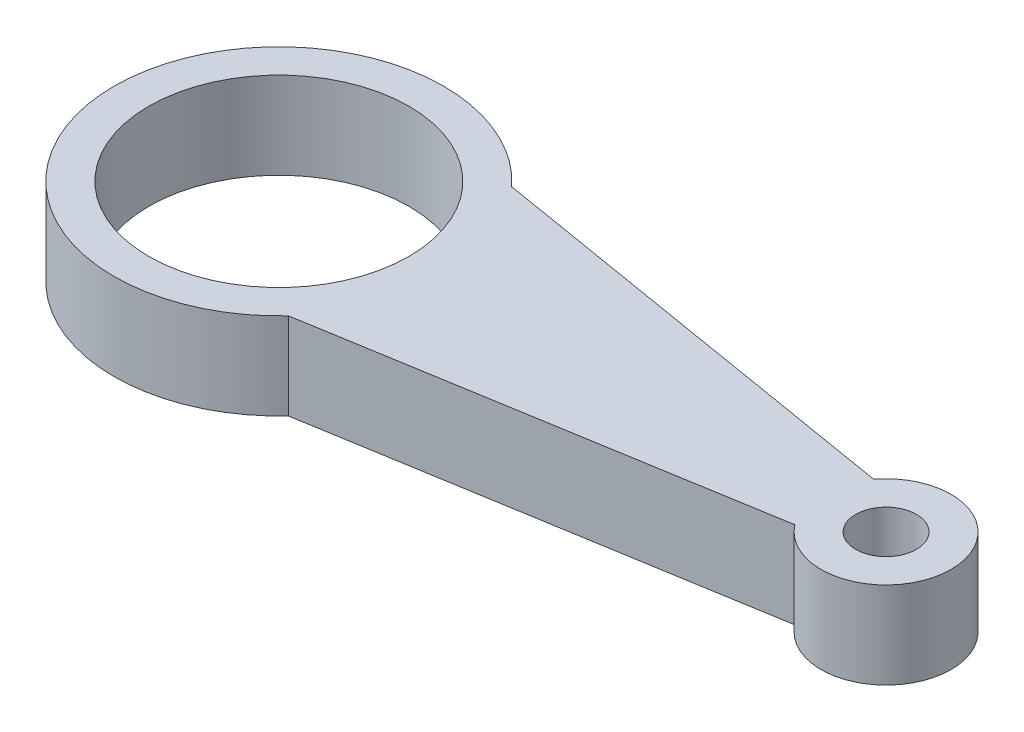
SolidWorks part; units mm, degrees
ref_plane "Front Plane" through (0, 0, 0) normal (0, 0, 1) x (1, 0, 0)
ref_plane "Top Plane" through (0, 0, 0) normal (0, 1, 0) x (1, 0, 0)
ref_plane "Right Plane" through (0, 0, 0) normal (1, 0, 0) x (0, 0, -1)
sketch "Sketch1" plane through (0, 0, 0) normal (0, 1, 0) x (1, 0, 0)
  line L0 (-49.1456, 0) -> (183.8958, 0) construction
  line L1 (27.9355, 25.7606) -> (128.0638, 9.0844)
  line L2 (27.9355, -25.7606) -> (128.0638, -9.0844)
  circle A0 centre (0, 0) radius 30
  arc A1 (27.9355, 25.7606) -> (27.9355, -25.7606) centre (0, 0) ccw
  circle A2 centre (140, 0) radius 7
  arc A3 (128.0638, -9.0844) -> (128.0638, 9.0844) centre (140, 0) ccw
  dimension "D1" = 60
  dimension "D2" = 76
  dimension "D3" = 14
  dimension "D4" = 30
  dimension "D5" = 140
extrude "Boss-Extrude1" add sketch "Sketch1" along normal mid plane 20
sketch "Sketch2" plane through (0, 10, 0) normal (0, 1, 0) x (1, 0, 0)
  line L0 (30, 0) -> (133, 0) construction
  circle A0 centre (0, 0) radius 30 construction
  circle A1 centre (140, 0) radius 7 construction
  point P12 (30, 0)
